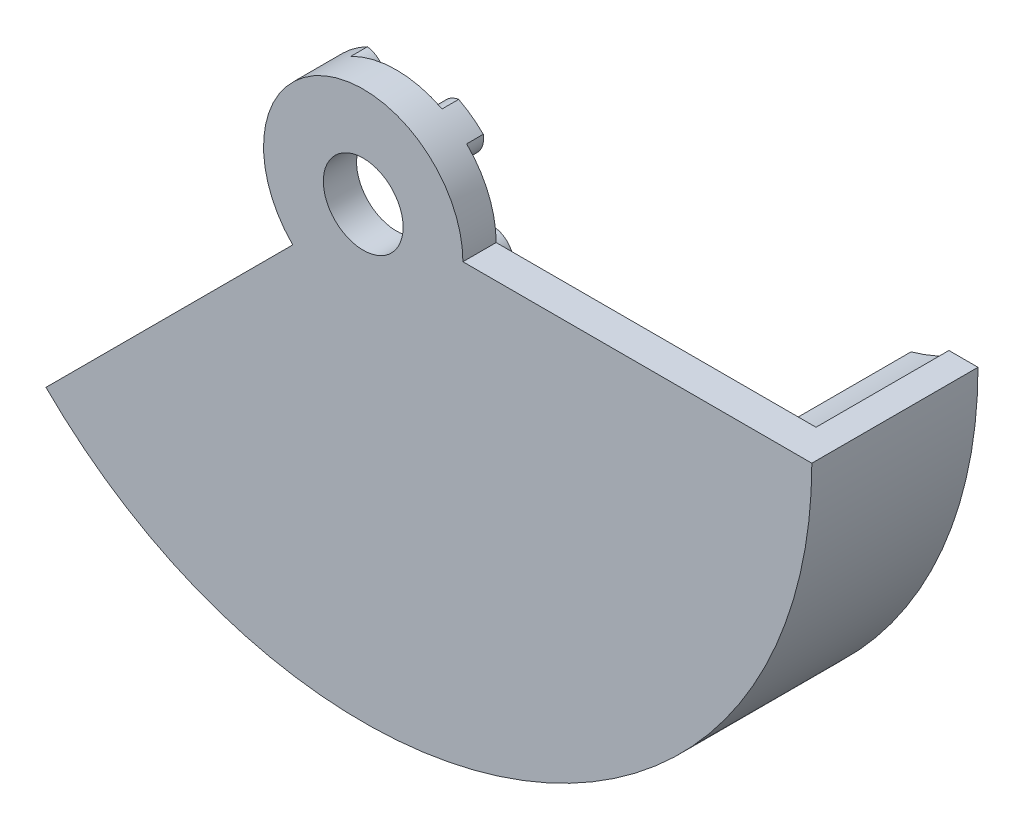
SolidWorks part; units mm, degrees
ref_plane "Front Plane" through (0, 0, 0) normal (0, 0, 1) x (1, 0, 0)
ref_plane "Top Plane" through (0, 0, 0) normal (0, 1, 0) x (1, 0, 0)
ref_plane "Right Plane" through (0, 0, 0) normal (1, 0, 0) x (0, 0, -1)
sketch "Sketch4" plane through (0, 0, 0) normal (0, 0, 1) x (1, 0, 0)
  arc A0 (11.9321, 56.2483) -> (10.5015, 56.5329) centre (0, 0) ccw construction
  arc A1 (10.5015, 56.5329) -> (8.9782, 62.4843) centre (-19.1705, 52.1088) ccw construction
  arc A2 (8.9782, 62.4843) -> (7.4999, 62.6789) centre (0, 0) ccw construction
  arc A3 (7.4999, 62.6789) -> (4.4881, 57.3246) centre (32.004, 45.3715) ccw construction
  arc A4 (11.9321, 56.2483) -> (10.5015, 56.5329) centre (0, 0) ccw
  arc A5 (10.5015, 56.5329) -> (8.9782, 62.4843) centre (-19.1705, 52.1088) ccw
  arc A6 (8.9782, 62.4843) -> (7.4999, 62.6789) centre (0, 0) ccw
  arc A7 (7.4999, 62.6789) -> (4.4881, 57.3246) centre (32.004, 45.3715) ccw
  arc A8 (15.6169, 61.1637) -> (11.9321, 56.2483) centre (37.6524, 40.806) ccw
  arc A9 (17.0572, 60.7778) -> (15.6169, 61.1637) centre (0, 0) ccw
  arc A10 (17.7907, 54.6785) -> (17.0572, 60.7778) centre (-12.2049, 54.1652) ccw
  arc A11 (19.1719, 54.2097) -> (17.7907, 54.6785) centre (0, 0) ccw
  arc A12 (23.4668, 58.6021) -> (19.1719, 54.2097) centre (42.6565, 35.5423) ccw
  arc A13 (24.8444, 58.0314) -> (23.4668, 58.6021) centre (0, 0) ccw
  arc A14 (24.7754, 51.8886) -> (24.8444, 58.0314) centre (-5.0305, 55.2949) ccw
  arc A15 (26.0837, 51.2435) -> (24.7754, 51.8886) centre (0, 0) ccw
  arc A16 (30.9151, 55.0377) -> (26.0837, 51.2435) centre (46.9308, 29.6704) ccw
  arc A17 (32.2065, 54.2921) -> (30.9151, 55.0377) centre (0, 0) ccw
  arc A18 (31.3363, 48.2108) -> (32.2065, 54.2921) centre (2.2299, 55.4785) ccw
  arc A19 (32.5491, 47.4005) -> (31.3363, 48.2108) centre (0, 0) ccw
  arc A20 (37.8345, 50.5316) -> (32.5491, 47.4005) centre (50.4021, 23.2909) ccw
  arc A21 (39.0175, 49.6239) -> (37.8345, 50.5316) centre (0, 0) ccw
  arc A22 (37.361, 43.7082) -> (39.0175, 49.6239) centre (9.4522, 54.7128) ccw
  arc A23 (38.4577, 42.7464) -> (37.361, 43.7082) centre (0, 0) ccw
  arc A24 (44.1065, 45.1609) -> (38.4577, 42.7464) centre (53.0109, 16.5128) ccw
  arc A25 (45.1609, 44.1065) -> (44.1065, 45.1609) centre (0, 0) ccw
  arc A26 (42.7464, 38.4577) -> (45.1609, 44.1065) centre (16.5128, 53.0109) ccw
  arc A27 (43.7082, 37.361) -> (42.7464, 38.4577) centre (0, 0) ccw
  arc A28 (49.6239, 39.0175) -> (43.7082, 37.361) centre (54.7128, 9.4522) ccw
  arc A29 (50.5316, 37.8345) -> (49.6239, 39.0175) centre (0, 0) ccw
  arc A30 (47.4005, 32.5491) -> (50.5316, 37.8345) centre (23.2909, 50.4021) ccw
  arc A31 (48.2108, 31.3363) -> (47.4005, 32.5491) centre (0, 0) ccw
  arc A32 (54.2921, 32.2065) -> (48.2108, 31.3363) centre (55.4785, 2.2299) ccw
  arc A33 (55.0377, 30.9151) -> (54.2921, 32.2065) centre (0, 0) ccw
  arc A34 (51.2435, 26.0837) -> (55.0377, 30.9151) centre (29.6704, 46.9308) ccw
  arc A35 (51.8886, 24.7754) -> (51.2435, 26.0837) centre (0, 0) ccw
  arc A36 (58.0314, 24.8444) -> (51.8886, 24.7754) centre (55.2949, -5.0305) ccw
  arc A37 (58.6021, 23.4668) -> (58.0314, 24.8444) centre (0, 0) ccw
  arc A38 (54.2097, 19.1719) -> (58.6021, 23.4668) centre (35.5423, 42.6565) ccw
  arc A39 (54.6785, 17.7907) -> (54.2097, 19.1719) centre (0, 0) ccw
  arc A40 (60.7778, 17.0572) -> (54.6785, 17.7907) centre (54.1652, -12.2049) ccw
  arc A41 (61.1637, 15.6169) -> (60.7778, 17.0572) centre (0, 0) ccw
  arc A42 (56.2483, 11.9321) -> (61.1637, 15.6169) centre (40.806, 37.6524) ccw
  arc A43 (56.5329, 10.5015) -> (56.2483, 11.9321) centre (0, 0) ccw
  arc A44 (62.4843, 8.9782) -> (56.5329, 10.5015) centre (52.1088, -19.1705) ccw
  arc A45 (62.6789, 7.4999) -> (62.4843, 8.9782) centre (0, 0) ccw
  arc A46 (57.3246, 4.4881) -> (62.6789, 7.4999) centre (45.3715, 32.004) ccw
  arc A47 (57.42, 3.0326) -> (57.3246, 4.4881) centre (0, 0) ccw
  arc A48 (63.1216, 0.7455) -> (57.42, 3.0326) centre (49.1607, -25.8081) ccw
  arc A49 (63.1216, -0.7455) -> (63.1216, 0.7455) centre (0, 0) ccw
  arc A50 (57.42, -3.0326) -> (63.1216, -0.7455) centre (49.1607, 25.8081) ccw
  arc A51 (57.3246, -4.4881) -> (57.42, -3.0326) centre (0, 0) ccw
  arc A52 (62.6789, -7.4999) -> (57.3246, -4.4881) centre (45.3715, -32.004) ccw
  arc A53 (62.4843, -8.9782) -> (62.6789, -7.4999) centre (0, 0) ccw
  arc A54 (56.5329, -10.5015) -> (62.4843, -8.9782) centre (52.1088, 19.1705) ccw
  arc A55 (56.2483, -11.9321) -> (56.5329, -10.5015) centre (0, 0) ccw
  arc A56 (61.1637, -15.6169) -> (56.2483, -11.9321) centre (40.806, -37.6524) ccw
  arc A57 (60.7778, -17.0572) -> (61.1637, -15.6169) centre (0, 0) ccw
  arc A58 (54.6785, -17.7907) -> (60.7778, -17.0572) centre (54.1652, 12.2049) ccw
  arc A59 (54.2097, -19.1719) -> (54.6785, -17.7907) centre (0, 0) ccw
  arc A60 (58.6021, -23.4668) -> (54.2097, -19.1719) centre (35.5423, -42.6565) ccw
  arc A61 (58.0314, -24.8444) -> (58.6021, -23.4668) centre (0, 0) ccw
  arc A62 (51.8886, -24.7754) -> (58.0314, -24.8444) centre (55.2949, 5.0305) ccw
  arc A63 (51.2435, -26.0837) -> (51.8886, -24.7754) centre (0, 0) ccw
  arc A64 (55.0377, -30.9151) -> (51.2435, -26.0837) centre (29.6704, -46.9308) ccw
  arc A65 (54.2921, -32.2065) -> (55.0377, -30.9151) centre (0, 0) ccw
  arc A66 (48.2108, -31.3363) -> (54.2921, -32.2065) centre (55.4785, -2.2299) ccw
  arc A67 (47.4005, -32.5491) -> (48.2108, -31.3363) centre (0, 0) ccw
  arc A68 (50.5316, -37.8345) -> (47.4005, -32.5491) centre (23.2909, -50.4021) ccw
  arc A69 (49.6239, -39.0175) -> (50.5316, -37.8345) centre (0, 0) ccw
  arc A70 (43.7082, -37.361) -> (49.6239, -39.0175) centre (54.7128, -9.4522) ccw
  arc A71 (42.7464, -38.4577) -> (43.7082, -37.361) centre (0, 0) ccw
  arc A72 (45.1609, -44.1065) -> (42.7464, -38.4577) centre (16.5128, -53.0109) ccw
  arc A73 (44.1065, -45.1609) -> (45.1609, -44.1065) centre (0, 0) ccw
  arc A74 (38.4577, -42.7464) -> (44.1065, -45.1609) centre (53.0109, -16.5128) ccw
  arc A75 (37.361, -43.7082) -> (38.4577, -42.7464) centre (0, 0) ccw
  arc A76 (39.0175, -49.6239) -> (37.361, -43.7082) centre (9.4522, -54.7128) ccw
  arc A77 (37.8345, -50.5316) -> (39.0175, -49.6239) centre (0, 0) ccw
  arc A78 (32.5491, -47.4005) -> (37.8345, -50.5316) centre (50.4021, -23.2909) ccw
  arc A79 (31.3363, -48.2108) -> (32.5491, -47.4005) centre (0, 0) ccw
  arc A80 (32.2065, -54.2921) -> (31.3363, -48.2108) centre (2.2299, -55.4785) ccw
  arc A81 (30.9151, -55.0377) -> (32.2065, -54.2921) centre (0, 0) ccw
  arc A82 (26.0837, -51.2435) -> (30.9151, -55.0377) centre (46.9308, -29.6704) ccw
  arc A83 (24.7754, -51.8886) -> (26.0837, -51.2435) centre (0, 0) ccw
  arc A84 (24.8444, -58.0314) -> (24.7754, -51.8886) centre (-5.0305, -55.2949) ccw
  arc A85 (23.4668, -58.6021) -> (24.8444, -58.0314) centre (0, 0) ccw
  arc A86 (19.1719, -54.2097) -> (23.4668, -58.6021) centre (42.6565, -35.5423) ccw
  arc A87 (17.7907, -54.6785) -> (19.1719, -54.2097) centre (0, 0) ccw
  arc A88 (17.0572, -60.7778) -> (17.7907, -54.6785) centre (-12.2049, -54.1652) ccw
  arc A89 (15.6169, -61.1637) -> (17.0572, -60.7778) centre (0, 0) ccw
  arc A90 (11.9321, -56.2483) -> (15.6169, -61.1637) centre (37.6524, -40.806) ccw
  arc A91 (10.5015, -56.5329) -> (11.9321, -56.2483) centre (0, 0) ccw
  arc A92 (8.9782, -62.4843) -> (10.5015, -56.5329) centre (-19.1705, -52.1088) ccw
  arc A93 (7.4999, -62.6789) -> (8.9782, -62.4843) centre (0, 0) ccw
  arc A94 (4.4881, -57.3246) -> (7.4999, -62.6789) centre (32.004, -45.3715) ccw
  arc A95 (3.0326, -57.42) -> (4.4881, -57.3246) centre (0, 0) ccw
  arc A96 (0.7455, -63.1216) -> (3.0326, -57.42) centre (-25.8081, -49.1607) ccw
  arc A97 (-0.7455, -63.1216) -> (0.7455, -63.1216) centre (0, 0) ccw
  arc A98 (-3.0326, -57.42) -> (-0.7455, -63.1216) centre (25.8081, -49.1607) ccw
  arc A99 (-4.4881, -57.3246) -> (-3.0326, -57.42) centre (0, 0) ccw
  arc A100 (-7.4999, -62.6789) -> (-4.4881, -57.3246) centre (-32.004, -45.3715) ccw
  arc A101 (-8.9782, -62.4843) -> (-7.4999, -62.6789) centre (0, 0) ccw
  arc A102 (-10.5015, -56.5329) -> (-8.9782, -62.4843) centre (19.1705, -52.1088) ccw
  arc A103 (-11.9321, -56.2483) -> (-10.5015, -56.5329) centre (0, 0) ccw
  arc A104 (-15.6169, -61.1637) -> (-11.9321, -56.2483) centre (-37.6524, -40.806) ccw
  arc A105 (-17.0572, -60.7778) -> (-15.6169, -61.1637) centre (0, 0) ccw
  arc A106 (-17.7907, -54.6785) -> (-17.0572, -60.7778) centre (12.2049, -54.1652) ccw
  arc A107 (-19.1719, -54.2097) -> (-17.7907, -54.6785) centre (0, 0) ccw
  arc A108 (-23.4668, -58.6021) -> (-19.1719, -54.2097) centre (-42.6565, -35.5423) ccw
  arc A109 (-24.8444, -58.0314) -> (-23.4668, -58.6021) centre (0, 0) ccw
  arc A110 (-24.7754, -51.8886) -> (-24.8444, -58.0314) centre (5.0305, -55.2949) ccw
  arc A111 (-26.0837, -51.2435) -> (-24.7754, -51.8886) centre (0, 0) ccw
  arc A112 (-30.9151, -55.0377) -> (-26.0837, -51.2435) centre (-46.9308, -29.6704) ccw
  arc A113 (-32.2065, -54.2921) -> (-30.9151, -55.0377) centre (0, 0) ccw
  arc A114 (-31.3363, -48.2108) -> (-32.2065, -54.2921) centre (-2.2299, -55.4785) ccw
  arc A115 (-32.5491, -47.4005) -> (-31.3363, -48.2108) centre (0, 0) ccw
  arc A116 (-37.8345, -50.5316) -> (-32.5491, -47.4005) centre (-50.4021, -23.2909) ccw
  arc A117 (-39.0175, -49.6239) -> (-37.8345, -50.5316) centre (0, 0) ccw
  arc A118 (-37.361, -43.7082) -> (-39.0175, -49.6239) centre (-9.4522, -54.7128) ccw
  arc A119 (-38.4577, -42.7464) -> (-37.361, -43.7082) centre (0, 0) ccw
  arc A120 (-44.1065, -45.1609) -> (-38.4577, -42.7464) centre (-53.0109, -16.5128) ccw
  arc A121 (-45.1609, -44.1065) -> (-44.1065, -45.1609) centre (0, 0) ccw
  arc A122 (-42.7464, -38.4577) -> (-45.1609, -44.1065) centre (-16.5128, -53.0109) ccw
  arc A123 (-43.7082, -37.361) -> (-42.7464, -38.4577) centre (0, 0) ccw
  arc A124 (-49.6239, -39.0175) -> (-43.7082, -37.361) centre (-54.7128, -9.4522) ccw
  arc A125 (-50.5316, -37.8345) -> (-49.6239, -39.0175) centre (0, 0) ccw
  arc A126 (-47.4005, -32.5491) -> (-50.5316, -37.8345) centre (-23.2909, -50.4021) ccw
  arc A127 (-48.2108, -31.3363) -> (-47.4005, -32.5491) centre (0, 0) ccw
  arc A128 (-54.2921, -32.2065) -> (-48.2108, -31.3363) centre (-55.4785, -2.2299) ccw
  arc A129 (-55.0377, -30.9151) -> (-54.2921, -32.2065) centre (0, 0) ccw
  arc A130 (-51.2435, -26.0837) -> (-55.0377, -30.9151) centre (-29.6704, -46.9308) ccw
  arc A131 (-51.8886, -24.7754) -> (-51.2435, -26.0837) centre (0, 0) ccw
  arc A132 (-58.0314, -24.8444) -> (-51.8886, -24.7754) centre (-55.2949, 5.0305) ccw
  arc A133 (-58.6021, -23.4668) -> (-58.0314, -24.8444) centre (0, 0) ccw
  arc A134 (-54.2097, -19.1719) -> (-58.6021, -23.4668) centre (-35.5423, -42.6565) ccw
  arc A135 (-54.6785, -17.7907) -> (-54.2097, -19.1719) centre (0, 0) ccw
  arc A136 (-60.7778, -17.0572) -> (-54.6785, -17.7907) centre (-54.1652, 12.2049) ccw
  arc A137 (-61.1637, -15.6169) -> (-60.7778, -17.0572) centre (0, 0) ccw
  arc A138 (-56.2483, -11.9321) -> (-61.1637, -15.6169) centre (-40.806, -37.6524) ccw
  arc A139 (-56.5329, -10.5015) -> (-56.2483, -11.9321) centre (0, 0) ccw
  arc A140 (-62.4843, -8.9782) -> (-56.5329, -10.5015) centre (-52.1088, 19.1705) ccw
  arc A141 (-62.6789, -7.4999) -> (-62.4843, -8.9782) centre (0, 0) ccw
  arc A142 (-57.3246, -4.4881) -> (-62.6789, -7.4999) centre (-45.3715, -32.004) ccw
  arc A143 (-57.42, -3.0326) -> (-57.3246, -4.4881) centre (0, 0) ccw
  arc A144 (-63.1216, -0.7455) -> (-57.42, -3.0326) centre (-49.1607, 25.8081) ccw
  arc A145 (-63.1216, 0.7455) -> (-63.1216, -0.7455) centre (0, 0) ccw
  arc A146 (-57.42, 3.0326) -> (-63.1216, 0.7455) centre (-49.1607, -25.8081) ccw
  arc A147 (-57.3246, 4.4881) -> (-57.42, 3.0326) centre (0, 0) ccw
  arc A148 (-62.6789, 7.4999) -> (-57.3246, 4.4881) centre (-45.3715, 32.004) ccw
  arc A149 (-62.4843, 8.9782) -> (-62.6789, 7.4999) centre (0, 0) ccw
  arc A150 (-56.5329, 10.5015) -> (-62.4843, 8.9782) centre (-52.1088, -19.1705) ccw
  arc A151 (-56.2483, 11.9321) -> (-56.5329, 10.5015) centre (0, 0) ccw
  arc A152 (-61.1637, 15.6169) -> (-56.2483, 11.9321) centre (-40.806, 37.6524) ccw
  arc A153 (-60.7778, 17.0572) -> (-61.1637, 15.6169) centre (0, 0) ccw
  arc A154 (-54.6785, 17.7907) -> (-60.7778, 17.0572) centre (-54.1652, -12.2049) ccw
  arc A155 (-54.2097, 19.1719) -> (-54.6785, 17.7907) centre (0, 0) ccw
  arc A156 (-58.6021, 23.4668) -> (-54.2097, 19.1719) centre (-35.5423, 42.6565) ccw
  arc A157 (-58.0314, 24.8444) -> (-58.6021, 23.4668) centre (0, 0) ccw
  arc A158 (-51.8886, 24.7754) -> (-58.0314, 24.8444) centre (-55.2949, -5.0305) ccw
  arc A159 (-51.2435, 26.0837) -> (-51.8886, 24.7754) centre (0, 0) ccw
  arc A160 (-55.0377, 30.9151) -> (-51.2435, 26.0837) centre (-29.6704, 46.9308) ccw
  arc A161 (-54.2921, 32.2065) -> (-55.0377, 30.9151) centre (0, 0) ccw
  arc A162 (-48.2108, 31.3363) -> (-54.2921, 32.2065) centre (-55.4785, 2.2299) ccw
  arc A163 (-47.4005, 32.5491) -> (-48.2108, 31.3363) centre (0, 0) ccw
  arc A164 (-50.5316, 37.8345) -> (-47.4005, 32.5491) centre (-23.2909, 50.4021) ccw
  arc A165 (-49.6239, 39.0175) -> (-50.5316, 37.8345) centre (0, 0) ccw
  arc A166 (-43.7082, 37.361) -> (-49.6239, 39.0175) centre (-54.7128, 9.4522) ccw
  arc A167 (-42.7464, 38.4577) -> (-43.7082, 37.361) centre (0, 0) ccw
  arc A168 (-45.1609, 44.1065) -> (-42.7464, 38.4577) centre (-16.5128, 53.0109) ccw
  arc A169 (-44.1065, 45.1609) -> (-45.1609, 44.1065) centre (0, 0) ccw
  arc A170 (-38.4577, 42.7464) -> (-44.1065, 45.1609) centre (-53.0109, 16.5128) ccw
  arc A171 (-37.361, 43.7082) -> (-38.4577, 42.7464) centre (0, 0) ccw
  arc A172 (-39.0175, 49.6239) -> (-37.361, 43.7082) centre (-9.4522, 54.7128) ccw
  arc A173 (-37.8345, 50.5316) -> (-39.0175, 49.6239) centre (0, 0) ccw
  arc A174 (-32.5491, 47.4005) -> (-37.8345, 50.5316) centre (-50.4021, 23.2909) ccw
  arc A175 (-31.3363, 48.2108) -> (-32.5491, 47.4005) centre (0, 0) ccw
  arc A176 (-32.2065, 54.2921) -> (-31.3363, 48.2108) centre (-2.2299, 55.4785) ccw
  arc A177 (-30.9151, 55.0377) -> (-32.2065, 54.2921) centre (0, 0) ccw
  arc A178 (-26.0837, 51.2435) -> (-30.9151, 55.0377) centre (-46.9308, 29.6704) ccw
  arc A179 (-24.7754, 51.8886) -> (-26.0837, 51.2435) centre (0, 0) ccw
  arc A180 (-24.8444, 58.0314) -> (-24.7754, 51.8886) centre (5.0305, 55.2949) ccw
  arc A181 (-23.4668, 58.6021) -> (-24.8444, 58.0314) centre (0, 0) ccw
  arc A182 (-19.1719, 54.2097) -> (-23.4668, 58.6021) centre (-42.6565, 35.5423) ccw
  arc A183 (-17.7907, 54.6785) -> (-19.1719, 54.2097) centre (0, 0) ccw
  arc A184 (-17.0572, 60.7778) -> (-17.7907, 54.6785) centre (12.2049, 54.1652) ccw
  arc A185 (-15.6169, 61.1637) -> (-17.0572, 60.7778) centre (0, 0) ccw
  arc A186 (-11.9321, 56.2483) -> (-15.6169, 61.1637) centre (-37.6524, 40.806) ccw
  arc A187 (-10.5015, 56.5329) -> (-11.9321, 56.2483) centre (0, 0) ccw
  arc A188 (-8.9782, 62.4843) -> (-10.5015, 56.5329) centre (19.1705, 52.1088) ccw
  arc A189 (-7.4999, 62.6789) -> (-8.9782, 62.4843) centre (0, 0) ccw
  arc A190 (-4.4881, 57.3246) -> (-7.4999, 62.6789) centre (-32.004, 45.3715) ccw
  arc A191 (-3.0326, 57.42) -> (-4.4881, 57.3246) centre (0, 0) ccw
  arc A192 (-0.7455, 63.1216) -> (-3.0326, 57.42) centre (25.8081, 49.1607) ccw
  arc A193 (0.7455, 63.1216) -> (-0.7455, 63.1216) centre (0, 0) ccw
  arc A194 (3.0326, 57.42) -> (0.7455, 63.1216) centre (-25.8081, 49.1607) ccw
  arc A195 (4.4881, 57.3246) -> (3.0326, 57.42) centre (0, 0) ccw
  circle A196 centre (0, 0) radius 67.5
  dimension "D1" = 48
extrude "Boss-Extrude1" add sketch "Sketch4" along normal blind 50
sketch "Sketch5" plane through (0, 0, 0) normal (0, 0, -1) x (-1, 0, 0)
  line L0 (0, 0) -> (-67.5, 0)
  line L1 (0, 0) -> (47.7297, -47.7297)
  circle A0 centre (0, 0) radius 67.5 construction
  arc A1 (47.7297, -47.7297) -> (-67.5, 0) centre (0, 0) ccw
extrude "Cut-Extrude2" cut sketch "Sketch5" against normal blind 250 contours L1 A1 L0 region at (-8.1028, 19.562, 0)
sketch "Sketch6" plane through (0, 0, 50) normal (0, 0, 1) x (1, 0, 0)
  line L0 (0, 0) -> (67.5, 0)
  line L1 (0, 0) -> (-47.7297, -47.7297)
  arc A0 (67.5, 0) -> (-47.7297, -47.7297) centre (0, 0) cw
  arc A1 (-47.7297, -47.7297) -> (67.5, 0) centre (0, 0) ccw construction
extrude "Boss-Extrude2" add sketch "Sketch6" along normal blind 5 contours A0 L0 L1 region at (13.5047, -32.6033, 50)
sketch "Sketch7" plane through (0, 0, 55) normal (0, 0, 1) x (1, 0, 0)
  circle A0 centre (0, 0) radius 6
extrude "Cut-Extrude3" cut sketch "Sketch7" against normal blind 5
sketch "Sketch8" plane through (0, 0, 55) normal (0, 0, 1) x (1, 0, 0)
  circle A0 centre (0, 0) radius 6
  circle A1 centre (0, 0) radius 10
extrude "Boss-Extrude3" add sketch "Sketch8" against normal blind 5
sketch "Sketch9" plane through (0, 0, 0) normal (0, 0, -1) x (-1, 0, 0)
  line L2 (47.7297, -47.7297) -> (44.6368, -44.6368)
  line L3 (-63.126, 0) -> (-67.5, 0)
  line L4 (47.7297, -47.7297) -> (44.6368, -44.6368)
  line L5 (-63.126, 0) -> (-67.5, 0)
  arc A74 (-67.5, 0) -> (47.7297, -47.7297) centre (0, 0) ccw
  arc A75 (44.1065, -45.1609) -> (44.6368, -44.6368) centre (0, 0) ccw
  arc A76 (38.4577, -42.7464) -> (44.1065, -45.1609) centre (53.0109, -16.5128) ccw
  arc A77 (37.361, -43.7082) -> (38.4577, -42.7464) centre (0, 0) ccw
  arc A78 (39.0175, -49.6239) -> (37.361, -43.7082) centre (9.4522, -54.7128) ccw
  arc A79 (37.8345, -50.5316) -> (39.0175, -49.6239) centre (0, 0) ccw
  arc A80 (32.5491, -47.4005) -> (37.8345, -50.5316) centre (50.4021, -23.2909) ccw
  arc A81 (31.3363, -48.2108) -> (32.5491, -47.4005) centre (0, 0) ccw
  arc A82 (32.2065, -54.2921) -> (31.3363, -48.2108) centre (2.2299, -55.4785) ccw
  arc A83 (30.9151, -55.0377) -> (32.2065, -54.2921) centre (0, 0) ccw
  arc A84 (26.0837, -51.2435) -> (30.9151, -55.0377) centre (46.9308, -29.6704) ccw
  arc A85 (24.7754, -51.8886) -> (26.0837, -51.2435) centre (0, 0) ccw
  arc A86 (24.8444, -58.0314) -> (24.7754, -51.8886) centre (-5.0305, -55.2949) ccw
  arc A87 (23.4668, -58.6021) -> (24.8444, -58.0314) centre (0, 0) ccw
  arc A88 (19.1719, -54.2097) -> (23.4668, -58.6021) centre (42.6565, -35.5423) ccw
  arc A89 (17.7907, -54.6785) -> (19.1719, -54.2097) centre (0, 0) ccw
  arc A90 (17.0572, -60.7778) -> (17.7907, -54.6785) centre (-12.2049, -54.1652) ccw
  arc A91 (15.6169, -61.1637) -> (17.0572, -60.7778) centre (0, 0) ccw
  arc A92 (11.9321, -56.2483) -> (15.6169, -61.1637) centre (37.6524, -40.806) ccw
  arc A93 (10.5015, -56.5329) -> (11.9321, -56.2483) centre (0, 0) ccw
  arc A94 (8.9782, -62.4843) -> (10.5015, -56.5329) centre (-19.1705, -52.1088) ccw
  arc A95 (7.4999, -62.6789) -> (8.9782, -62.4843) centre (0, 0) ccw
  arc A96 (4.4881, -57.3246) -> (7.4999, -62.6789) centre (32.004, -45.3715) ccw
  arc A97 (3.0326, -57.42) -> (4.4881, -57.3246) centre (0, 0) ccw
  arc A98 (0.7455, -63.1216) -> (3.0326, -57.42) centre (-25.8081, -49.1607) ccw
  arc A99 (-0.7455, -63.1216) -> (0.7455, -63.1216) centre (0, 0) ccw
  arc A100 (-3.0326, -57.42) -> (-0.7455, -63.1216) centre (25.8081, -49.1607) ccw
  arc A101 (-4.4881, -57.3246) -> (-3.0326, -57.42) centre (0, 0) ccw
  arc A102 (-7.4999, -62.6789) -> (-4.4881, -57.3246) centre (-32.004, -45.3715) ccw
  arc A103 (-8.9782, -62.4843) -> (-7.4999, -62.6789) centre (0, 0) ccw
  arc A104 (-10.5015, -56.5329) -> (-8.9782, -62.4843) centre (19.1705, -52.1088) ccw
  arc A105 (-11.9321, -56.2483) -> (-10.5015, -56.5329) centre (0, 0) ccw
  arc A106 (-15.6169, -61.1637) -> (-11.9321, -56.2483) centre (-37.6524, -40.806) ccw
  arc A107 (-17.0572, -60.7778) -> (-15.6169, -61.1637) centre (0, 0) ccw
  arc A108 (-17.7907, -54.6785) -> (-17.0572, -60.7778) centre (12.2049, -54.1652) ccw
  arc A109 (-19.1719, -54.2097) -> (-17.7907, -54.6785) centre (0, 0) ccw
  arc A110 (-23.4668, -58.6021) -> (-19.1719, -54.2097) centre (-42.6565, -35.5423) ccw
  arc A111 (-24.8444, -58.0314) -> (-23.4668, -58.6021) centre (0, 0) ccw
  arc A112 (-24.7754, -51.8886) -> (-24.8444, -58.0314) centre (5.0305, -55.2949) ccw
  arc A113 (-26.0837, -51.2435) -> (-24.7754, -51.8886) centre (0, 0) ccw
  arc A114 (-30.9151, -55.0377) -> (-26.0837, -51.2435) centre (-46.9308, -29.6704) ccw
  arc A115 (-32.2065, -54.2921) -> (-30.9151, -55.0377) centre (0, 0) ccw
  arc A116 (-31.3363, -48.2108) -> (-32.2065, -54.2921) centre (-2.2299, -55.4785) ccw
  arc A117 (-32.5491, -47.4005) -> (-31.3363, -48.2108) centre (0, 0) ccw
  arc A118 (-37.8345, -50.5316) -> (-32.5491, -47.4005) centre (-50.4021, -23.2909) ccw
  arc A119 (-39.0175, -49.6239) -> (-37.8345, -50.5316) centre (0, 0) ccw
  arc A120 (-37.361, -43.7082) -> (-39.0175, -49.6239) centre (-9.4522, -54.7128) ccw
  arc A121 (-38.4577, -42.7464) -> (-37.361, -43.7082) centre (0, 0) ccw
  arc A122 (-44.1065, -45.1609) -> (-38.4577, -42.7464) centre (-53.0109, -16.5128) ccw
  arc A123 (-45.1609, -44.1065) -> (-44.1065, -45.1609) centre (0, 0) ccw
  arc A124 (-42.7464, -38.4577) -> (-45.1609, -44.1065) centre (-16.5128, -53.0109) ccw
  arc A125 (-43.7082, -37.361) -> (-42.7464, -38.4577) centre (0, 0) ccw
  arc A126 (-49.6239, -39.0175) -> (-43.7082, -37.361) centre (-54.7128, -9.4522) ccw
  arc A127 (-50.5316, -37.8345) -> (-49.6239, -39.0175) centre (0, 0) ccw
  arc A128 (-47.4005, -32.5491) -> (-50.5316, -37.8345) centre (-23.2909, -50.4021) ccw
  arc A129 (-48.2108, -31.3363) -> (-47.4005, -32.5491) centre (0, 0) ccw
  arc A130 (-54.2921, -32.2065) -> (-48.2108, -31.3363) centre (-55.4785, -2.2299) ccw
  arc A131 (-55.0377, -30.9151) -> (-54.2921, -32.2065) centre (0, 0) ccw
  arc A132 (-51.2435, -26.0837) -> (-55.0377, -30.9151) centre (-29.6704, -46.9308) ccw
  arc A133 (-51.8886, -24.7754) -> (-51.2435, -26.0837) centre (0, 0) ccw
  arc A134 (-58.0314, -24.8444) -> (-51.8886, -24.7754) centre (-55.2949, 5.0305) ccw
  arc A135 (-58.6021, -23.4668) -> (-58.0314, -24.8444) centre (0, 0) ccw
  arc A136 (-54.2097, -19.1719) -> (-58.6021, -23.4668) centre (-35.5423, -42.6565) ccw
  arc A137 (-54.6785, -17.7907) -> (-54.2097, -19.1719) centre (0, 0) ccw
  arc A138 (-60.7778, -17.0572) -> (-54.6785, -17.7907) centre (-54.1652, 12.2049) ccw
  arc A139 (-61.1637, -15.6169) -> (-60.7778, -17.0572) centre (0, 0) ccw
  arc A140 (-56.2483, -11.9321) -> (-61.1637, -15.6169) centre (-40.806, -37.6524) ccw
  arc A141 (-56.5329, -10.5015) -> (-56.2483, -11.9321) centre (0, 0) ccw
  arc A142 (-62.4843, -8.9782) -> (-56.5329, -10.5015) centre (-52.1088, 19.1705) ccw
  arc A143 (-62.6789, -7.4999) -> (-62.4843, -8.9782) centre (0, 0) ccw
  arc A144 (-57.3246, -4.4881) -> (-62.6789, -7.4999) centre (-45.3715, -32.004) ccw
  arc A145 (-57.42, -3.0326) -> (-57.3246, -4.4881) centre (0, 0) ccw
  arc A146 (-63.1216, -0.7455) -> (-57.42, -3.0326) centre (-49.1607, 25.8081) ccw
  arc A147 (-63.126, 0) -> (-63.1216, -0.7455) centre (0, 0) ccw
  arc A148 (-67.5, 0) -> (47.7297, -47.7297) centre (0, 0) ccw
  arc A149 (44.1065, -45.1609) -> (44.6368, -44.6368) centre (0, 0) ccw
  arc A150 (38.4577, -42.7464) -> (44.1065, -45.1609) centre (53.0109, -16.5128) ccw
  arc A151 (37.361, -43.7082) -> (38.4577, -42.7464) centre (0, 0) ccw
  arc A152 (39.0175, -49.6239) -> (37.361, -43.7082) centre (9.4522, -54.7128) ccw
  arc A153 (37.8345, -50.5316) -> (39.0175, -49.6239) centre (0, 0) ccw
  arc A154 (32.5491, -47.4005) -> (37.8345, -50.5316) centre (50.4021, -23.2909) ccw
  arc A155 (31.3363, -48.2108) -> (32.5491, -47.4005) centre (0, 0) ccw
  arc A156 (32.2065, -54.2921) -> (31.3363, -48.2108) centre (2.2299, -55.4785) ccw
  arc A157 (30.9151, -55.0377) -> (32.2065, -54.2921) centre (0, 0) ccw
  arc A158 (26.0837, -51.2435) -> (30.9151, -55.0377) centre (46.9308, -29.6704) ccw
  arc A159 (24.7754, -51.8886) -> (26.0837, -51.2435) centre (0, 0) ccw
  arc A160 (24.8444, -58.0314) -> (24.7754, -51.8886) centre (-5.0305, -55.2949) ccw
  arc A161 (23.4668, -58.6021) -> (24.8444, -58.0314) centre (0, 0) ccw
  arc A162 (19.1719, -54.2097) -> (23.4668, -58.6021) centre (42.6565, -35.5423) ccw
  arc A163 (17.7907, -54.6785) -> (19.1719, -54.2097) centre (0, 0) ccw
  arc A164 (17.0572, -60.7778) -> (17.7907, -54.6785) centre (-12.2049, -54.1652) ccw
  arc A165 (15.6169, -61.1637) -> (17.0572, -60.7778) centre (0, 0) ccw
  arc A166 (11.9321, -56.2483) -> (15.6169, -61.1637) centre (37.6524, -40.806) ccw
  arc A167 (10.5015, -56.5329) -> (11.9321, -56.2483) centre (0, 0) ccw
  arc A168 (8.9782, -62.4843) -> (10.5015, -56.5329) centre (-19.1705, -52.1088) ccw
  arc A169 (7.4999, -62.6789) -> (8.9782, -62.4843) centre (0, 0) ccw
  arc A170 (4.4881, -57.3246) -> (7.4999, -62.6789) centre (32.004, -45.3715) ccw
  arc A171 (3.0326, -57.42) -> (4.4881, -57.3246) centre (0, 0) ccw
  arc A172 (0.7455, -63.1216) -> (3.0326, -57.42) centre (-25.8081, -49.1607) ccw
  arc A173 (-0.7455, -63.1216) -> (0.7455, -63.1216) centre (0, 0) ccw
  arc A174 (-3.0326, -57.42) -> (-0.7455, -63.1216) centre (25.8081, -49.1607) ccw
  arc A175 (-4.4881, -57.3246) -> (-3.0326, -57.42) centre (0, 0) ccw
  arc A176 (-7.4999, -62.6789) -> (-4.4881, -57.3246) centre (-32.004, -45.3715) ccw
  arc A177 (-8.9782, -62.4843) -> (-7.4999, -62.6789) centre (0, 0) ccw
  arc A178 (-10.5015, -56.5329) -> (-8.9782, -62.4843) centre (19.1705, -52.1088) ccw
  arc A179 (-11.9321, -56.2483) -> (-10.5015, -56.5329) centre (0, 0) ccw
  arc A180 (-15.6169, -61.1637) -> (-11.9321, -56.2483) centre (-37.6524, -40.806) ccw
  arc A181 (-17.0572, -60.7778) -> (-15.6169, -61.1637) centre (0, 0) ccw
  arc A182 (-17.7907, -54.6785) -> (-17.0572, -60.7778) centre (12.2049, -54.1652) ccw
  arc A183 (-19.1719, -54.2097) -> (-17.7907, -54.6785) centre (0, 0) ccw
  arc A184 (-23.4668, -58.6021) -> (-19.1719, -54.2097) centre (-42.6565, -35.5423) ccw
  arc A185 (-24.8444, -58.0314) -> (-23.4668, -58.6021) centre (0, 0) ccw
  arc A186 (-24.7754, -51.8886) -> (-24.8444, -58.0314) centre (5.0305, -55.2949) ccw
  arc A187 (-26.0837, -51.2435) -> (-24.7754, -51.8886) centre (0, 0) ccw
  arc A188 (-30.9151, -55.0377) -> (-26.0837, -51.2435) centre (-46.9308, -29.6704) ccw
  arc A189 (-32.2065, -54.2921) -> (-30.9151, -55.0377) centre (0, 0) ccw
  arc A190 (-31.3363, -48.2108) -> (-32.2065, -54.2921) centre (-2.2299, -55.4785) ccw
  arc A191 (-32.5491, -47.4005) -> (-31.3363, -48.2108) centre (0, 0) ccw
  arc A192 (-37.8345, -50.5316) -> (-32.5491, -47.4005) centre (-50.4021, -23.2909) ccw
  arc A193 (-39.0175, -49.6239) -> (-37.8345, -50.5316) centre (0, 0) ccw
  arc A194 (-37.361, -43.7082) -> (-39.0175, -49.6239) centre (-9.4522, -54.7128) ccw
  arc A195 (-38.4577, -42.7464) -> (-37.361, -43.7082) centre (0, 0) ccw
  arc A196 (-44.1065, -45.1609) -> (-38.4577, -42.7464) centre (-53.0109, -16.5128) ccw
  arc A197 (-45.1609, -44.1065) -> (-44.1065, -45.1609) centre (0, 0) ccw
  arc A198 (-42.7464, -38.4577) -> (-45.1609, -44.1065) centre (-16.5128, -53.0109) ccw
  arc A199 (-43.7082, -37.361) -> (-42.7464, -38.4577) centre (0, 0) ccw
  arc A200 (-49.6239, -39.0175) -> (-43.7082, -37.361) centre (-54.7128, -9.4522) ccw
  arc A201 (-50.5316, -37.8345) -> (-49.6239, -39.0175) centre (0, 0) ccw
  arc A202 (-47.4005, -32.5491) -> (-50.5316, -37.8345) centre (-23.2909, -50.4021) ccw
  arc A203 (-48.2108, -31.3363) -> (-47.4005, -32.5491) centre (0, 0) ccw
  arc A204 (-54.2921, -32.2065) -> (-48.2108, -31.3363) centre (-55.4785, -2.2299) ccw
  arc A205 (-55.0377, -30.9151) -> (-54.2921, -32.2065) centre (0, 0) ccw
  arc A206 (-51.2435, -26.0837) -> (-55.0377, -30.9151) centre (-29.6704, -46.9308) ccw
  arc A207 (-51.8886, -24.7754) -> (-51.2435, -26.0837) centre (0, 0) ccw
  arc A208 (-58.0314, -24.8444) -> (-51.8886, -24.7754) centre (-55.2949, 5.0305) ccw
  arc A209 (-58.6021, -23.4668) -> (-58.0314, -24.8444) centre (0, 0) ccw
  arc A210 (-54.2097, -19.1719) -> (-58.6021, -23.4668) centre (-35.5423, -42.6565) ccw
  arc A211 (-54.6785, -17.7907) -> (-54.2097, -19.1719) centre (0, 0) ccw
  arc A212 (-60.7778, -17.0572) -> (-54.6785, -17.7907) centre (-54.1652, 12.2049) ccw
  arc A213 (-61.1637, -15.6169) -> (-60.7778, -17.0572) centre (0, 0) ccw
  arc A214 (-56.2483, -11.9321) -> (-61.1637, -15.6169) centre (-40.806, -37.6524) ccw
  arc A215 (-56.5329, -10.5015) -> (-56.2483, -11.9321) centre (0, 0) ccw
  arc A216 (-62.4843, -8.9782) -> (-56.5329, -10.5015) centre (-52.1088, 19.1705) ccw
  arc A217 (-62.6789, -7.4999) -> (-62.4843, -8.9782) centre (0, 0) ccw
  arc A218 (-57.3246, -4.4881) -> (-62.6789, -7.4999) centre (-45.3715, -32.004) ccw
  arc A219 (-57.42, -3.0326) -> (-57.3246, -4.4881) centre (0, 0) ccw
  arc A220 (-63.1216, -0.7455) -> (-57.42, -3.0326) centre (-49.1607, 25.8081) ccw
  arc A221 (-63.126, 0) -> (-63.1216, -0.7455) centre (0, 0) ccw
  dimension "D1" = 0
extrude "Cut-Extrude5" cut sketch "Sketch9" against normal blind 30
sketch "Sketch10" plane through (0, 0, 50) normal (0, 0, -1) x (-1, 0, 0)
  arc A0 (2.2906, -14.8241) -> (13.3907, -6.7594) centre (0, 0) ccw
  arc A1 (8.7662, -4.8119) -> (13.3907, -6.7594) centre (11.8882, -3.8627) ccw
  arc A2 (1.8675, -9.8241) -> (8.7662, -4.8119) centre (0, 0) ccw
  arc A3 (2.2906, -14.8241) -> (1.8675, -9.8241) centre (0, -12.5) ccw
  arc A4 (-8.7662, -4.8119) -> (-1.8675, -9.8241) centre (0, 0) ccw
  arc A5 (-13.3907, -6.7594) -> (-8.7662, -4.8119) centre (-11.8882, -3.8627) ccw
  arc A6 (-13.3907, -6.7594) -> (-2.2906, -14.8241) centre (0, 0) ccw
  arc A7 (-1.8675, -9.8241) -> (-2.2906, -14.8241) centre (0, -12.5) ccw
  arc A8 (-7.2853, 6.8501) -> (-9.9203, -1.2597) centre (0, 0) ccw
  arc A9 (-10.5665, 10.6465) -> (-7.2853, 6.8501) centre (-7.3473, 10.1127) ccw
  arc A10 (-10.5665, 10.6465) -> (-14.8064, -2.4024) centre (0, 0) ccw
  arc A11 (-9.9203, -1.2597) -> (-14.8064, -2.4024) centre (-11.8882, -3.8627) ccw
  arc A12 (4.2636, 9.0455) -> (-4.2636, 9.0455) centre (0, 0) ccw
  arc A13 (6.8602, 13.3393) -> (4.2636, 9.0455) centre (7.3473, 10.1127) ccw
  arc A14 (6.8602, 13.3393) -> (-6.8602, 13.3393) centre (0, 0) ccw
  arc A15 (-4.2636, 9.0455) -> (-6.8602, 13.3393) centre (-7.3473, 10.1127) ccw
  arc A16 (9.9203, -1.2597) -> (7.2853, 6.8501) centre (0, 0) ccw
  arc A17 (14.8064, -2.4024) -> (9.9203, -1.2597) centre (11.8882, -3.8627) ccw
  arc A18 (14.8064, -2.4024) -> (10.5665, 10.6465) centre (0, 0) ccw
  arc A19 (7.2853, 6.8501) -> (10.5665, 10.6465) centre (7.3473, 10.1127) ccw
  arc A20 (7.2853, 6.8501) -> (4.2636, 9.0455) centre (0, 0) ccw
  arc A21 (10.5665, 10.6465) -> (6.8602, 13.3393) centre (0, 0) ccw
  arc A22 (8.7662, -4.8119) -> (9.9203, -1.2597) centre (0, 0) ccw
  arc A23 (13.3907, -6.7594) -> (14.8064, -2.4024) centre (0, 0) ccw
  arc A24 (-1.8675, -9.8241) -> (1.8675, -9.8241) centre (0, 0) ccw
  arc A25 (-2.2906, -14.8241) -> (2.2906, -14.8241) centre (0, 0) ccw
  arc A26 (-9.9203, -1.2597) -> (-8.7662, -4.8119) centre (0, 0) ccw
  arc A27 (-14.8064, -2.4024) -> (-13.3907, -6.7594) centre (0, 0) ccw
  arc A28 (-4.2636, 9.0455) -> (-7.2853, 6.8501) centre (0, 0) ccw
  arc A29 (-6.8602, 13.3393) -> (-10.5665, 10.6465) centre (0, 0) ccw
  dimension "D1" = 5
sketch "Sketch11" plane through (0, 0, 50) normal (0, 0, -1) x (-1, 0, 0)
  circle A0 centre (0, 0) radius 15
  circle A1 centre (0, 0) radius 6
extrude "Boss-Extrude4" add sketch "Sketch11" against normal blind 5
extrude "Boss-Extrude5" add sketch "Sketch10" along normal blind 2.5 contours A15 A29 A9 A28 | A19 A21 A13 A20 | A1 A23 A17 A22 | A7 A25 A3 A24 | A11 A27 A5 A26 region at (0, -12.4574, 50) region at (-11.8477, -3.8496, 50) region at (11.8477, -3.8496, 50) region at (-7.3223, 10.0783, 50) region at (7.3223, 10.0783, 50)
